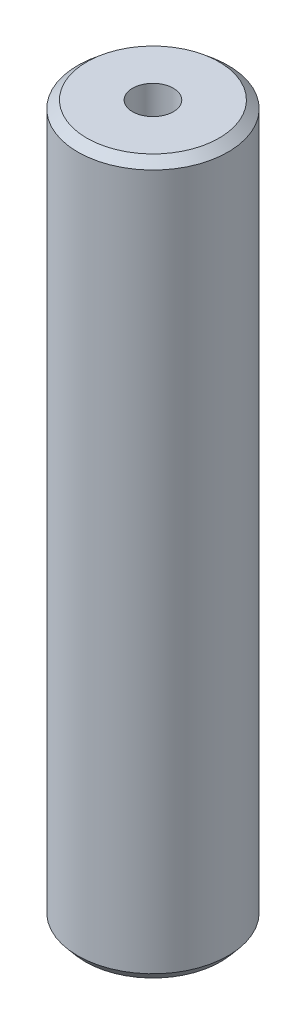
SolidWorks part; units mm, degrees
ref_plane "Front Plane" through (0, 0, 0) normal (0, 0, 1) x (1, 0, 0)
ref_plane "Top Plane" through (0, 0, 0) normal (0, 1, 0) x (1, 0, 0)
ref_plane "Right Plane" through (0, 0, 0) normal (1, 0, 0) x (0, 0, -1)
sketch "Sketch1" plane through (0, 0, 0) normal (0, 1, 0) x (1, 0, 0)
  circle A0 centre (0, 0) radius 7.5
  dimension "SHAFT_OD" = 15
extrude "Boss-Extrude1" add sketch "Sketch1" along normal blind 71.1373
sketch "Sketch2" plane through (0, 0, 0) normal (0, 1, 0) x (1, 0, 0)
  circle A0 centre (0, 0) radius 2.0368
  dimension "BORE_D" = 4.0736
extrude "Cut-Extrude1" cut sketch "Sketch2" along normal through all
chamfer "Chamfer1" distance 0.7549 angle 50 2 edges at (0, 71.1373, 7.5) (0, 0, 7.5) first distance on face at (0, 71.1373, 7.5) first distance on face at (0, 0, 2.0368)
